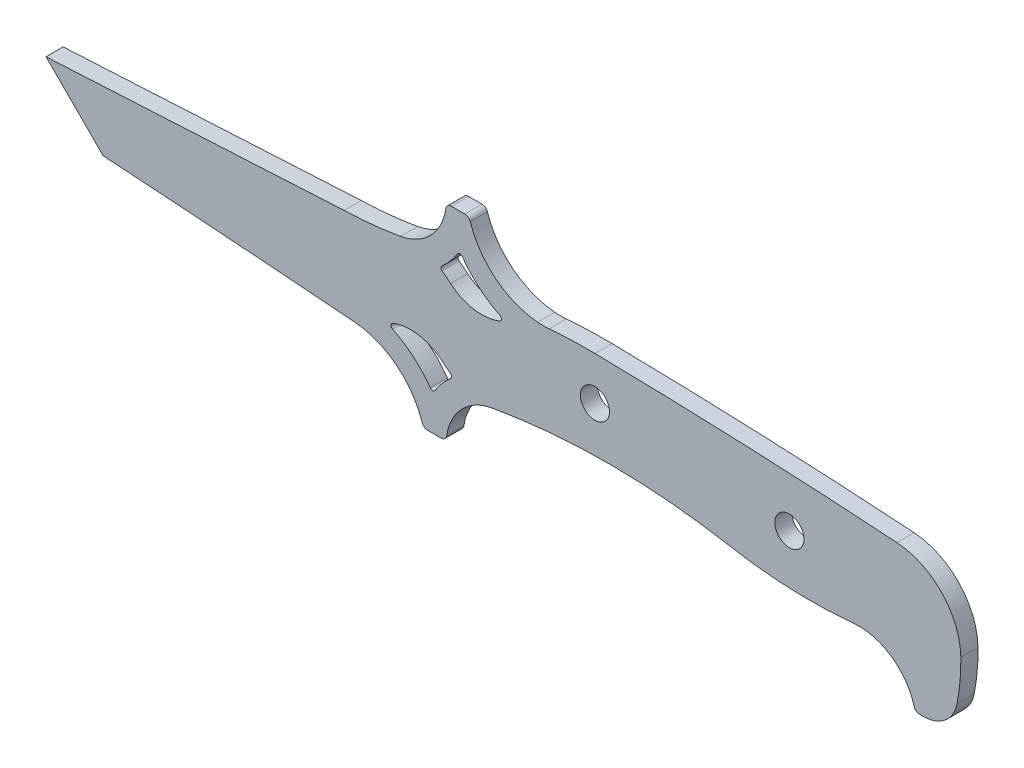
SolidWorks part; units mm, degrees
ref_plane "前视基准面" through (0, 0, 0) normal (0, 0, 1) x (1, 0, 0)
ref_plane "上视基准面" through (0, 0, 0) normal (0, 1, 0) x (1, 0, 0)
ref_plane "右视基准面" through (0, 0, 0) normal (1, 0, 0) x (0, 0, -1)
sketch "草图1" plane through (0, 0, 0) normal (0, 0, 1) x (1, 0, 0)
  line L0 (-25.5902, 0) -> (-5.9672, 0) construction
  line L1 (0, 18.5328) -> (0, -16.9262) construction
  line L2 (-70, 0) -> (-60, -10)
  line L3 (-4, -23.2) -> (0, -23.2)
  line L4 (4, 12.8) -> (0, 12.8)
  line L5 (90, 7.5343) -> (90, -10.4544) construction
  line L6 (82, -23.2) -> (88, -23.2)
  line L7 (-61.0097, -3.3334) -> (-58.2369, -6.1062)
  arc A0 (-70, 0) -> (-17.8579, 2.8) centre (10, -1002.8746) cw
  arc A1 (-60, -10) -> (-16, -13.2) centre (-240.1427, -2791.0621) cw
  arc A2 (-16, -13.2) -> (-4, -23.2) centre (-17.0899, -26.7079) cw
  arc A3 (-17.8579, 2.8) -> (0, -5.2) centre (-17.2336, -19.7379) cw
  arc A4 (18, -12.8749) -> (0, -5.2) centre (16.9672, 9.648) cw
  arc A5 (0, -23.2) -> (8, -14.2) centre (9.684, -23.7525) cw
  arc A6 (8, -14.2) -> (49.4396, -14.2835) centre (28.4857, -130.404) cw
  arc A7 (16, 2.8) -> (4, 12.8) centre (17.0899, 16.3079) cw
  arc A8 (0, 12.8) -> (-8, 3.8) centre (-9.684, 13.3525) cw
  arc A9 (89.9953, -10.9458) -> (88, -23.2) centre (54.9016, -11.5212) cw
  arc A11 (16, 2.8) -> (18, 2.8) centre (17, 15.1933) ccw
  arc A12 (18, 2.8) -> (26, 3.0585) centre (24.6793, -79.9778) cw
  arc A14 (-17.8579, 2.8) -> (0, 3.1361) centre (10, -1002.8746) cw construction
  arc A15 (26, 3.0585) -> (78.8177, 0.8293) centre (10, -1002.8746) cw
  arc A16 (0, 3.1361) -> (13.7999, 3.1786) centre (10, -1002.8746) cw construction
  arc A17 (13.7999, 3.1786) -> (26, 3.0585) centre (10, -1002.8746) cw construction
  arc A18 (88, 0.1575) -> (90, 0) centre (10, -1002.8746) cw construction
  arc A19 (71.2421, -15.1936) -> (82, -23.2) centre (72.1916, -25.1484) cw
  arc A20 (-17.8579, 2.8) -> (-8, 3.8) centre (-19.7285, 70.3294) ccw
  arc A21 (89.9953, -10.9458) -> (78.8177, 0.8293) centre (77.9969, -11.1426) ccw
  arc A22 (71.2421, -15.1936) -> (49.4396, -14.2835) centre (63.6461, 64.445) cw
  arc A23 (-10.3422, -10.505) -> (-2.3422, -17.191) centre (-17.0899, -26.7079) cw
  arc A24 (-2.3422, -17.191) -> (1.2378, -12.9662) centre (9.684, -23.7525) cw
  arc A25 (-10.3422, -10.505) -> (-0.7622, -11.4347) centre (-6.2282, -17.9345) cw
  arc A26 (-0.7622, -11.4347) -> (1.2378, -12.9662) centre (16.9672, 9.648) ccw
  arc A27 (0.7622, 1.0347) -> (-1.2378, 2.5662) centre (-16.9672, -20.048) ccw
  arc A28 (2.3422, 6.791) -> (-1.2378, 2.5662) centre (-9.684, 13.3525) cw
  arc A29 (10.3422, 0.105) -> (2.3422, 6.791) centre (17.0899, 16.3079) cw
  arc A30 (10.3422, 0.105) -> (0.7622, 1.0347) centre (6.2282, 7.5345) cw
  arc A31 (-61.0097, -3.3334) -> (-59, -3.1927) centre (10, -1002.8746) cw
  arc A32 (-59, -3.1927) -> (-44, 1.7355) centre (-61.21, 28.826) ccw
  arc A33 (-58.2369, -6.1062) -> (-26, -8.3994) centre (-240.1427, -2791.0621) cw
  arc A34 (-26, -8.3994) -> (-7.1666, -17.4786) centre (-28.2045, -37.0451) cw
  circle A35 centre (60, -6.8) radius 2.55
  circle A36 centre (26, -4.5) radius 2.55
  point P16 (-17.8579, 2.8)
  point P58 (65, -18.2)
  dimension "D1" = 70
  dimension "D5" = 2.8
  dimension "D6" = 2
  dimension "D8" = 8
  dimension "D12" = 6
  dimension "D18" = 10
  dimension "D24" = 12
  dimension "D25" = 80
  dimension "D26" = 4
  dimension "D27" = 4
  dimension "D28" = 5
  dimension "D29" = 2
  dimension "D32" = 4
  dimension "D34" = 4
  dimension "D37" = 26
  dimension "D38" = 5.1
  dimension "D39" = 5.1
  dimension "D3" = 45
  dimension "D4" = 10
  dimension "D9" = 4
  dimension "D10" = 16
  dimension "D11" = 10
  dimension "D13" = 26
  dimension "D14" = 18
  dimension "D15" = 10
  dimension "D16" = 25
  dimension "D17" = 5
  dimension "D19" = 2.8
  dimension "D20" = 36
  dimension "D21" = 18
  dimension "D22" = 9
  dimension "D23" = 2
  dimension "D30" = 8
  dimension "D33" = 4
  dimension "D35" = 26
  dimension "D36" = 15
  dimension "D40" = 6.8
  dimension "D41" = 30
  dimension "D42" = 26
  dimension "D43" = 4.5
  dimension "D44" = 90
  dimension "D7" = 2
  dimension "D31" = 2
sketch "草图3" plane through (0, 0, 0) normal (0, 0, 1) x (1, 0, 0)
  line L0 (-69, 0.0537) -> (-17.8579, 2.8)
  line L1 (-70, 0) -> (-60, -10) construction
  line L2 (-4, -23.2) -> (0, -23.2) construction
  line L3 (82, -23.2) -> (88, -23.2) construction
  line L4 (4, 12.8) -> (0, 12.8) construction
  line L5 (-69, 0.0537) -> (-70, 0)
  line L6 (-70, 0) -> (-60, -10)
  line L7 (-4, -23.2) -> (0, -23.2)
  line L8 (82, -23.2) -> (88, -23.2)
  line L9 (4, 12.8) -> (0, 12.8)
  arc A7 (-16, -13.2) -> (-60, -10) centre (-240.1427, -2791.0621) ccw construction
  arc A8 (-4, -23.2) -> (-16, -13.2) centre (-17.0899, -26.7079) ccw construction
  arc A9 (8, -14.2) -> (0, -23.2) centre (9.684, -23.7525) ccw construction
  arc A10 (49.4396, -14.2835) -> (8, -14.2) centre (28.4857, -130.404) ccw construction
  arc A11 (49.4396, -14.2835) -> (71.2421, -15.1936) centre (63.6461, 64.445) ccw construction
  arc A12 (82, -23.2) -> (71.2421, -15.1936) centre (72.1916, -25.1484) ccw construction
  arc A13 (88, -23.2) -> (89.9953, -10.9458) centre (54.9016, -11.5212) ccw construction
  arc A14 (89.9953, -10.9458) -> (78.8177, 0.8293) centre (77.9969, -11.1426) ccw construction
  arc A15 (78.8177, 0.8293) -> (26, 3.0585) centre (10, -1002.8746) ccw construction
  arc A16 (26, 3.0585) -> (18, 2.8) centre (24.6793, -79.9778) ccw construction
  arc A17 (16, 2.8) -> (18, 2.8) centre (17, 15.1933) ccw construction
  arc A18 (4, 12.8) -> (16, 2.8) centre (17.0899, 16.3079) ccw construction
  arc A19 (-8, 3.8) -> (0, 12.8) centre (-9.684, 13.3525) ccw construction
  arc A20 (-17.8579, 2.8) -> (-8, 3.8) centre (-19.7285, 70.3294) ccw construction
  arc A36 (-16, -13.2) -> (-60, -10) centre (-240.1427, -2791.0621) ccw
  arc A37 (-4, -23.2) -> (-16, -13.2) centre (-17.0899, -26.7079) ccw
  arc A38 (8, -14.2) -> (0, -23.2) centre (9.684, -23.7525) ccw
  arc A39 (49.4396, -14.2835) -> (8, -14.2) centre (28.4857, -130.404) ccw
  arc A40 (49.4396, -14.2835) -> (71.2421, -15.1936) centre (63.6461, 64.445) ccw
  arc A41 (82, -23.2) -> (71.2421, -15.1936) centre (72.1916, -25.1484) ccw
  arc A42 (88, -23.2) -> (89.9953, -10.9458) centre (54.9016, -11.5212) ccw
  arc A43 (89.9953, -10.9458) -> (78.8177, 0.8293) centre (77.9969, -11.1426) ccw
  arc A44 (78.8177, 0.8293) -> (26, 3.0585) centre (10, -1002.8746) ccw
  arc A45 (26, 3.0585) -> (18, 2.8) centre (24.6793, -79.9778) ccw
  arc A46 (16, 2.8) -> (18, 2.8) centre (17, 15.1933) ccw
  arc A47 (4, 12.8) -> (16, 2.8) centre (17.0899, 16.3079) ccw
  arc A48 (-8, 3.8) -> (0, 12.8) centre (-9.684, 13.3525) ccw
  arc A49 (-17.8579, 2.8) -> (-8, 3.8) centre (-19.7285, 70.3294) ccw
  point P0 (-69, 0.0537)
  dimension "D1" = 1
extrude "凸台-拉伸1" add sketch "草图3" along normal mid plane 3
extrude "切除-拉伸1" cut sketch "草图1" against normal through all both and the other way through all contours A30 A29 A28 A27 | A26 A25 A23 A24 region at (-3.912, -12.3789, 0) region at (3.912, 1.9789, 0)
fillet "圆角2" radius 0.5 6 edges at (-10.3422, -10.505, 0) (-2.3422, -17.191, 0) (1.2378, -12.9662, 0) (10.3422, 0.105, 0) (2.3422, 6.791, 0) (-1.2378, 2.5662, 0)
extrude "切除-拉伸2" cut sketch "草图1<3>" against normal through all both and the other way through all contours A36 | A35
sketch "草图1<3>" plane through (0, 0, 0) normal (0, 0, 1) x (1, 0, 0) same geometry as "草图1"
fillet "圆角3" radius 1 5 edges at (0, -23.2, 0) (-4, -23.2, 0) (4, 12.8, 0) (0, 12.8, 0) (82, -23.2, 0)
fillet "圆角4" radius 6 1 edges at (88, -23.2, 0)
